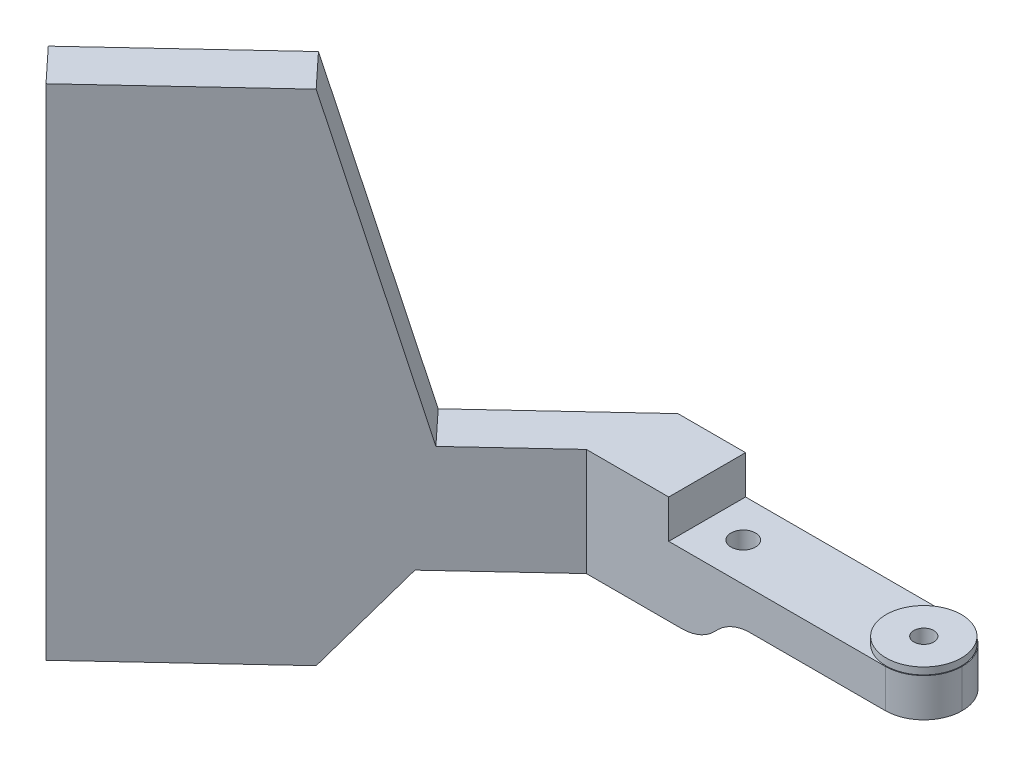
SolidWorks part; units mm, degrees
ref_plane "Front" through (0, 0, 0) normal (0, 0, 1) x (1, 0, 0)
ref_plane "Top" through (0, 0, 0) normal (0, 1, 0) x (1, 0, 0)
ref_plane "Right" through (0, 0, 0) normal (1, 0, 0) x (0, 0, -1)
sketch "Sketch1" plane through (0, 0, 0) normal (0, 1, 0) x (1, 0, 0)
  line L0 (0, 10) -> (0, 0)
  line L1 (0, 0) -> (42, 0)
  line L3 (0, 10) -> (42, 10)
  line L4 (42, 0) -> (42, 10)
  line L9 (0, 10) -> (-42.4185, -29.5559)
  line L10 (-42.4185, -29.5559) -> (-38.3265, -33.944)
  line L11 (0, 10) -> (4.092, 5.6119)
  line L12 (-38.3265, -33.944) -> (4.092, 5.6119)
  line L13 (0, 0) -> (-1.926, 0)
  line L14 (-1.926, 0) -> (0, 1.796)
  line L15 (0, 1.796) -> (0, 0)
  dimension "D1" = 10
  dimension "D2" = 42
  dimension "D3" = 223
  dimension "D4" = 58
  dimension "D5" = 6
  dimension "D6" = 270
extrude "Boss-Extrude1" add sketch "Sketch1" along normal blind 5 contours L10 L12 L1 L0 L9 | L1 L12 L11 L0 | L12 L1 L4 L3 L11 | L13 L0 L12 region at (1.364, 0, -5.8026) region at (-20.2035, 0, 12.8728) region at (21.8174, 0, -4.9666) region at (-0.642, 0, -0.5987)
fillet "Fillet1" radius 5 2 edges at (42, 2.5, 0) (42, 2.5, -10)
sketch "Sketch2" plane through (0, 5, 0) normal (0, 1, 0) x (1, 0, 0)
  circle A0 centre (37, 5) radius 1.3
extrude "Cut-Extrude1" cut sketch "Sketch2" against normal blind 10
sketch "Sketch3" plane through (0, 5, 0) normal (0, 1, 0) x (1, 0, 0)
  line L0 (-42.4185, -29.5559) -> (-38.3265, -33.944)
  line L1 (-38.3265, -33.944) -> (-20.1263, -16.972)
  line L2 (-38.3265, -33.944) -> (-1.926, 0) construction
  line L3 (-20.1263, -16.972) -> (-24.2183, -12.5839)
  line L4 (0, 10) -> (-42.4185, -29.5559) construction
  line L5 (-24.2183, -12.5839) -> (-42.4185, -29.5559)
extrude "Boss-Extrude2" add sketch "Sketch3" along normal blind 45
sketch "Sketch4" plane through (0, 0, 0) normal (0, -1, 0) x (1, 0, 0)
  line L0 (-42.4185, 29.5559) -> (-38.3265, 33.944)
  line L1 (-38.3265, 33.944) -> (-20.1263, 16.972)
  line L2 (-38.3265, 33.944) -> (-1.926, 0) construction
  line L3 (-20.1263, 16.972) -> (-24.2183, 12.5839)
  line L4 (0, -10) -> (-42.4185, 29.5559) construction
  line L5 (-24.2183, 12.5839) -> (-42.4185, 29.5559)
extrude "Boss-Extrude3" add sketch "Sketch4" along normal blind 15
sketch "Sketch5" plane through (-4.9878, 0, -5.3488) normal (-0.682, 0, -0.7314) x (-0.7314, 0, 0.682)
  line L0 (26.2943, -15) -> (26.2943, 0)
  line L1 (26.2943, 0) -> (13.889, 0)
  line L2 (-6.82, 0) -> (26.2943, 0) construction
  line L3 (13.889, 0) -> (26.2943, -15)
  line L4 (13.889, 5) -> (26.2943, 50)
  line L5 (-6.82, 5) -> (26.2943, 5) construction
  line L6 (26.2943, 50) -> (26.2943, 5)
  line L7 (26.2943, 5) -> (13.889, 5)
extrude "Boss-Extrude4" add sketch "Sketch5" against normal blind 6
sketch "Sketch6" plane through (0, 0, 0) normal (0, -1, 0) x (1, 0, 0)
  circle A0 centre (37, -5) radius 4.9
  circle A1 centre (37, -5) radius 1.3
extrude "Boss-Extrude5" add sketch "Sketch6" against normal blind 5.9
sketch "Sketch8" plane through (0, 0, 0) normal (0, -1, 0) x (1, 0, 0)
  line L0 (0, -10) -> (-19.6819, 8.3537)
  line L1 (-24.2183, 12.5839) -> (-15.1456, 4.1235) construction
  line L6 (-19.6819, 8.3537) -> (-15.5899, 12.7418)
  line L7 (-20.1263, 16.972) -> (-11.0536, 8.5116) construction
  line L8 (-15.5899, 12.7418) -> (8.7977, -10)
  line L9 (0, -10) -> (37, -10) construction
  line L10 (8.7977, -10) -> (0, -10)
extrude "Boss-Extrude6" add sketch "Sketch8" along normal blind 4
sketch "Sketch9" plane through (0, 5, 0) normal (0, 1, 0) x (1, 0, 0)
  line L3 (-17.565, -6.3796) -> (-24.2183, -12.5839) construction
  line L4 (-20.8916, -9.4817) -> (0, 10)
  line L6 (-20.8916, -9.4817) -> (-16.7996, -13.8699)
  line L7 (-20.1263, -16.972) -> (-11.0536, -8.5116) construction
  line L9 (-16.7996, -13.8699) -> (8.7977, 10)
  line L10 (0, 10) -> (37, 10) construction
  line L11 (8.7977, 10) -> (0, 10)
  line L12 (37, 0) -> (-1.926, 0) construction
  line L13 (8.7977, 0) -> (-1.926, 0)
  line L14 (-1.926, 0) -> (8.7977, 10)
  line L15 (8.7977, 10) -> (17.9505, 10)
  line L16 (17.9505, 10) -> (17.9505, 0)
  line L17 (17.9505, 0) -> (8.7977, 0)
  line M3 (-1.926, 0) -> (37, 0)
  line M6 (37, 10) -> (0, 10)
sketch "Sketch10" plane through (0, 5, 0) normal (0, 1, 0) x (1, 0, 0)
  line L0 (8.7977, 10) -> (8.7977, 0)
  line L1 (8.7977, 0) -> (-1.926, 0)
  line L2 (-1.926, 0) -> (-16.7996, -13.8699)
  line L3 (-16.7996, -13.8699) -> (-20.8916, -9.4817)
  line L4 (-20.8916, -9.4817) -> (0, 10)
  line L5 (0, 10) -> (8.7977, 10)
extrude "Boss-Extrude7" add sketch "Sketch10" along normal blind 5
extrude "Boss-Extrude8" add sketch "Sketch9" against normal blind 9 contours L16 L9 M6 M3 region at (10.3631, 5, -4.3843)
chamfer "Chamfer1" distance 5 angle 45 1 edges at (17.9505, -4, -5)
fillet "Fillet2" radius 6 2 edges at (16.9505, 0, -5) (12.9505, -4, -5)
sketch "Sketch11" plane through (0, 5, 0) normal (0, 1, 0) x (1, 0, 0)
  circle A0 centre (13.5, 5) radius 1.6
extrude "Cut-Extrude2" cut sketch "Sketch11" against normal blind 10
